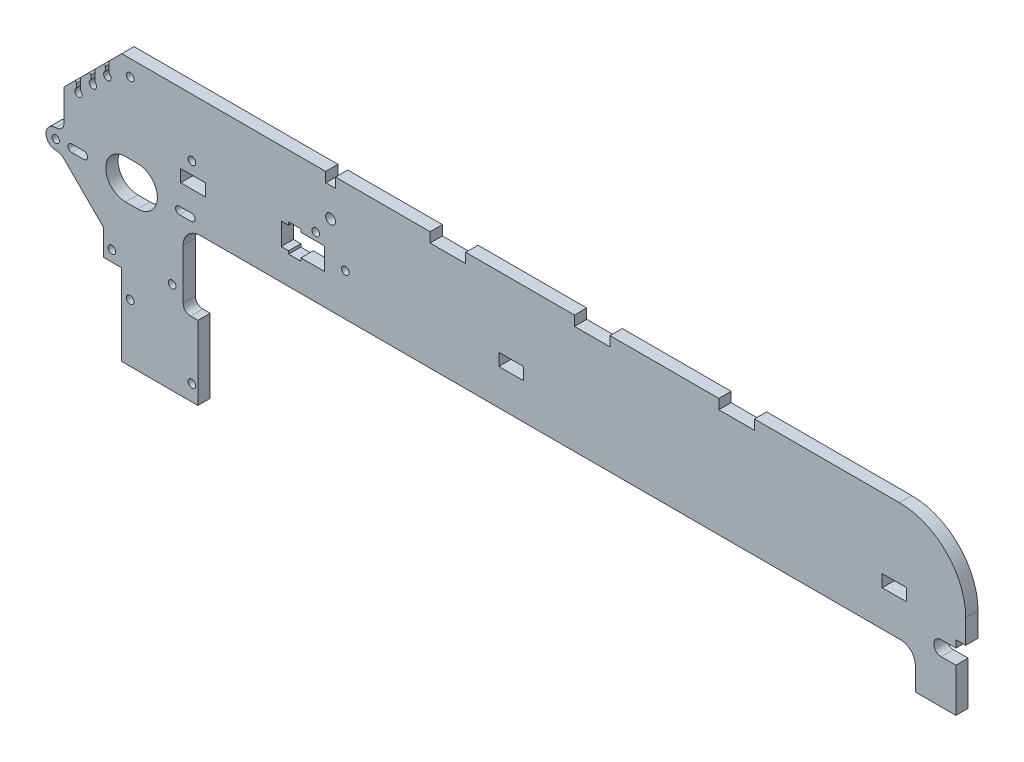
SolidWorks part; units mm, degrees
material "6061-T6 Black anodised"
ref_plane "Front Plane" through (0, 0, 0) normal (0, 0, 1) x (1, 0, 0)
ref_plane "Top Plane" through (0, 0, 0) normal (0, 1, 0) x (1, 0, 0)
ref_plane "Right Plane" through (0, 0, 0) normal (1, 0, 0) x (0, 0, -1)
sketch "Sketch1" plane through (0, 0, 0) normal (0, 0, 1) x (1, 0, 0)
  line L0 (-19.5, 0) -> (36.1968, 0) construction
  line L1 (-1.5, 32) -> (20.5, 32) construction
  line L2 (-21.9203, 0) -> (-30, 0) construction
  line L3 (-6.5, 43.5) -> (-6.5, 28.8553) construction
  line L4 (-1.5, 43.5) -> (20.5, 43.5) construction
  line L5 (310, 43.5) -> (251, 43.5)
  line L6 (21.9203, 0) -> (0, 21.9203) construction
  line L7 (0, 21.9203) -> (-21.9203, 0) construction
  line L8 (-21.9203, 0) -> (0, -21.9203) construction
  line L9 (0, -21.9203) -> (21.9203, 0) construction
  line L10 (316.5, -4.6) -> (316.5, -20)
  line L11 (-6.5, -65) -> (-6.5, -32)
  line L12 (-30, 5.3553) -> (-30, -5.3553) construction
  line L13 (327, 3.7) -> (333, 3.7)
  line L14 (316.5, -20) -> (333, -20)
  line L15 (18.5, -4.6) -> (316.5, -4.6)
  line L16 (34.5, -11.1) -> (59.432, -11.1) construction
  line L17 (333, 6.7) -> (333, 3.7)
  line L18 (9.5, 43.5) -> (9.5, -35.4767) construction
  line L19 (-1.5, 43.5) -> (20.5, 43.5) construction
  line L20 (-1.5, 43.5) -> (-1.5, 20.5) construction
  line L21 (-6.5, -65) -> (24.5, -65)
  line L22 (-1.5, 20.5) -> (20.5, 20.5) construction
  line L23 (327, -2.3) -> (333, -2.3)
  line L24 (333, -2.3) -> (333, -20)
  line L25 (333, 6.7) -> (337, 6.7)
  line L26 (337, 6.7) -> (337, 16.5)
  line L27 (18.5, -35) -> (18.5, -4.6)
  line L28 (20.5, 43.5) -> (20.5, 20.5) construction
  line L29 (17.5, 15) -> (17.5, 10)
  line L30 (17.5, 15) -> (27.5, 15)
  line L31 (27, 72.5933) -> (67, 72.5933) construction
  line L32 (147, 10) -> (157, 10)
  line L33 (147, 10) -> (147, 15)
  line L34 (17.5, 10) -> (27.5, 10)
  line L35 (27.5, 15) -> (27.5, 10)
  line L36 (147, 15) -> (157, 15)
  line L37 (157, 10) -> (157, 15)
  line L38 (303, 10) -> (313, 10)
  line L39 (303, 10) -> (303, 15)
  line L40 (303, 15) -> (313, 15)
  line L41 (313, 10) -> (313, 15)
  line L42 (27, 72.5933) -> (27, -81.6129) construction
  line L43 (27, -81.6129) -> (67, -81.6129) construction
  line L44 (67, 72.5933) -> (67, -81.6129) construction
  line L45 (-1.5, -52.5) -> (20.5, -52.5) construction
  line L46 (-1.5, -65) -> (20.5, -65) construction
  line L47 (-1.5, -65) -> (-1.5, -42) construction
  line L48 (-1.5, -42) -> (20.5, -42) construction
  line L49 (20.5, -65) -> (20.5, -42) construction
  line L50 (58.4277, 8) -> (61.4277, 8)
  line L51 (27.5, 12.5) -> (63.9277, 12.5) construction
  line L52 (61.4277, 6.8061) -> (66.4277, 6.8061)
  line L53 (61.4277, 6.8061) -> (61.4277, 8)
  line L54 (76, 8) -> (76, 17)
  line L55 (72.5, 20.1) -> (72.5, 7.1) construction
  line L56 (66.4277, 6.8061) -> (66.4277, 8)
  line L57 (66.4277, 8) -> (76, 8)
  line L58 (63.9277, 12.5) -> (76, 12.5) construction
  line L59 (66.4277, 18.1939) -> (61.4277, 18.1939)
  line L60 (66.4277, 6.8061) -> (61.4277, 18.1939) construction
  line L61 (61.4277, 6.8061) -> (66.4277, 18.1939) construction
  line L62 (18.5, -35) -> (24.5, -35)
  line L63 (66.4277, 17) -> (66.4277, 18.1939)
  line L64 (66.4277, 17) -> (76, 17)
  line L65 (61.4277, 17) -> (61.4277, 18.1939)
  line L66 (24.5, -35) -> (24.5, -65)
  line L67 (-14, -21.3553) -> (-30, -5.3553)
  line L68 (-14, -21.3553) -> (-14, -32)
  line L69 (-14, -32) -> (-6.5, -32)
  line L70 (119, 43.5) -> (119, 39.5)
  line L71 (119, 39.5) -> (133.5, 39.5)
  line L72 (177.75, 43.5) -> (177.75, 39.5)
  line L73 (119, 43.5) -> (80.5, 43.5)
  line L74 (-6.5, 28.8553) -> (-30, 5.3553) construction
  line L75 (177.75, 39.5) -> (192.25, 39.5)
  line L76 (159.788, -14) -> (-14, -14) construction
  line L77 (159.788, -14) -> (159.788, -26) construction
  line L78 (61.4277, 17) -> (58.4277, 17)
  line L79 (159.788, -26) -> (-14, -26) construction
  line L80 (-14, -14) -> (-14, -26) construction
  line L81 (58.4277, 17) -> (58.4277, 8)
  line L82 (159.788, -14) -> (-14, -26) construction
  line L83 (159.788, -26) -> (-14, -14) construction
  line L84 (192.25, 39.5) -> (192.25, 43.5)
  line L86 (236.5, 43.5) -> (236.5, 39.5)
  line L87 (236.5, 39.5) -> (251, 39.5)
  line L88 (251, 39.5) -> (251, 43.5)
  line L89 (177.75, 43.5) -> (133.5, 43.5)
  line L91 (-33.3631, 8.7185) -> (-33.3631, -8.7185) construction
  line L92 (76.5, 27.7514) -> (80.5, 27.7514) construction
  line L93 (133.5, 39.5) -> (133.5, 43.5)
  line L94 (76.5, 43.5) -> (76.5, 39.5)
  line L95 (76.5, 39.5) -> (80.5, 39.5)
  line L96 (80.5, 43.5) -> (80.5, 39.5)
  line L97 (76.5, 43.5) -> (-6.5, 43.5)
  line L98 (-30, 20) -> (-6.5, 43.5)
  line L99 (-30, 20) -> (-30, 7.3254)
  line L101 (119, 43.5) -> (177.75, 43.5) construction
  line L102 (192.25, 43.5) -> (236.5, 43.5)
  circle A0 centre (9.5, 34.5) radius 1.55 construction
  circle A1 centre (0, 0) radius 15.5 construction
  circle A2 centre (0, 21.9203) radius 1.5 construction
  circle A3 centre (21.9203, 0) radius 1.5
  circle A4 centre (0, -21.9203) radius 1.5 construction
  circle A5 centre (-21.9203, 0) radius 1.5
  circle A6 centre (0, 0) radius 5.5 construction
  arc A7 (337, 16.5) -> (310, 43.5) centre (310, 16.5) ccw
  circle A8 centre (0, 0) radius 8
  circle A9 centre (-3.05, 37) radius 1.55
  circle A10 centre (9.5, -57) radius 1.55 construction
  arc A11 (327, 3.7) -> (327, -2.3) centre (327, 0.7) ccw
  circle A12 centre (72, 0.4) radius 5 construction
  circle A13 centre (22, 38.5) radius 5 construction
  circle A14 centre (22, 38.5) radius 1.5 construction
  circle A15 centre (72, 0.4) radius 1.5 construction
  circle A16 centre (22.05, 20) radius 1.55
  circle A17 centre (-3.05, -41.5) radius 1.55
  circle A18 centre (22.05, -58.5) radius 1.55
  circle A19 centre (81.5, 20.1) radius 1.55 construction
  circle A20 centre (72.5, 20.1) radius 1.55
  circle A21 centre (84.5, 12.5) radius 1.55
  circle A22 centre (-10.5, -27.55) radius 1.55
  arc A23 (-33.3631, 3.9623) -> (-33.3631, -3.9623) centre (-33.3631, 0) ccw
  circle A24 centre (14, -27.55) radius 1.55
  circle A25 centre (-33.3631, 0) radius 1.5
  arc A26 (-33.3631, 3.9623) -> (-30, 7.3254) centre (-33.3631, 7.3254) ccw
  arc A27 (-33.3631, -3.9623) -> (-30, -5.3553) centre (-33.3631, -8.7185) cw
  circle A28 centre (78.5, 27.7514) radius 2
  point P18 (26.8692, -2.8293)
  point P19 (26.8692, 2.8293)
  point P108 (58.4277, 12.5)
  point P115 (72.894, -20)
  dimension "D2" = 31
  dimension "D3" = 3
  dimension "D4" = 11
  dimension "D12" = 16
  dimension "D20" = 3.1
  dimension "D22" = 8
  dimension "D25" = 3
  dimension "D28" = 6
  dimension "D32" = 10
  dimension "D38" = 3
  dimension "D14" = 31
  dimension "D41" = 3.1
  dimension "D44" = 9
  dimension "D45" = 3.1
  dimension "D53" = 6
  dimension "D18" = 7.5
  dimension "D57" = 3.1
  dimension "D69" = 4
  dimension "D7" = 9
  dimension "D11" = 16.5
  dimension "D17" = 15
  dimension "D8" = 65
  dimension "D9" = 43.5
  dimension "D5" = 9.5
  dimension "D6" = 4.6
  dimension "D10" = 6.5
  dimension "D13" = 337
  dimension "D15" = 23
  dimension "D16" = 25
  dimension "D19" = 30
  dimension "D21" = 9
  dimension "D23" = 21.1
  dimension "D24" = 15.4
  dimension "D26" = 6
  dimension "D27" = 4
  dimension "D29" = 67
  dimension "D30" = 17.5
  dimension "D31" = 40
  dimension "D33" = 5
  dimension "D34" = 10
  dimension "D35" = 24
  dimension "D36" = 180
  dimension "D37" = 22
  dimension "D39" = 5
  dimension "D40" = 12
  dimension "D42" = 11
  dimension "D43" = 6
  dimension "D46" = 3.1
  dimension "D47" = 9
  dimension "D48" = 15
  dimension "D49" = 0.7
  dimension "D50" = 5
  dimension "D51" = 12
  dimension "D52" = 3.5
  dimension "D54" = 4
  dimension "D55" = 12
  dimension "D56" = 20
  dimension "D58" = 4.5
  dimension "D59" = 3
  dimension "D60" = 9
  dimension "D61" = 30
  dimension "D62" = 12.5
  dimension "D63" = 52
  dimension "D64" = 14.5
  dimension "D68" = 4
  dimension "D70" = 6
  dimension "D72" = 58.75
  dimension "D67" = 3
extrude "Boss-Extrude1" add sketch "Sketch1" along normal blind 5
fillet "Fillet1" [suppressed] radius 8
fillet "Fillet2" radius 7 1 edges at (18.5, -4.6, 2.5)
fillet "Fillet3" radius 3 1 edges at (18.5, -35, 2.5)
sketch "Sketch2" plane through (0, 0, 5) normal (0, 0, 1) x (1, 0, 0)
  line L0 (21.9203, 0) -> (16.9203, 0) construction
  line L1 (21.9203, -1.5) -> (16.9203, -1.5)
  line L2 (21.9203, 1.5) -> (16.9203, 1.5)
  line L3 (0, 0) -> (-5, 0) construction
  line L4 (0, -8) -> (-5, -8)
  line L5 (0, 8) -> (-5, 8)
  line L6 (-21.9203, 0) -> (-26.9203, 0) construction
  line L7 (-21.9203, -1.5) -> (-26.9203, -1.5)
  line L8 (-21.9203, 1.5) -> (-26.9203, 1.5)
  arc A0 (21.9203, -1.5) -> (21.9203, 1.5) centre (21.9203, 0) ccw
  arc A1 (16.9203, 1.5) -> (16.9203, -1.5) centre (16.9203, 0) ccw
  arc A2 (0, -8) -> (0, 8) centre (0, 0) ccw
  arc A3 (-5, 8) -> (-5, -8) centre (-5, 0) ccw
  arc A4 (-21.9203, -1.5) -> (-21.9203, 1.5) centre (-21.9203, 0) ccw
  arc A5 (-26.9203, 1.5) -> (-26.9203, -1.5) centre (-26.9203, 0) ccw
  circle A6 centre (21.9203, 0) radius 1.5 construction
  circle A7 centre (0, 0) radius 8 construction
  point P4 (19.4203, 0)
  point P9 (-2.5, 0)
  point P16 (-24.4203, 0)
  dimension "D1" = 5
extrude "Cut-Extrude1" cut sketch "Sketch2" against normal through all
fillet "Fillet4" radius 6 1 edges at (316.5, -4.6, 2.5)
sketch "Sketch3" plane through (0, 0, 5) normal (0, 0, 1) x (1, 0, 0)
  line L0 (-12.375, 32.625) -> (-12.375, 37.625) construction
  line L1 (-13.125, 42.8359) -> (-11.625, 42.8359)
  line L2 (-13.125, 42.8359) -> (-13.125, 33.924)
  line L3 (-6.5, 43.5) -> (-30, 20) construction
  line L4 (-11.625, 42.8359) -> (-11.625, 33.924)
  line L5 (-13.125, 42.8359) -> (-11.625, 33.924) construction
  line L6 (-13.125, 33.924) -> (-11.625, 42.8359) construction
  line L7 (-6.5, 43.5) -> (-12.375, 37.625) construction
  line L8 (-12.375, 37.625) -> (-18.25, 31.75) construction
  line L9 (-18.25, 31.75) -> (-24.125, 25.875) construction
  line L10 (-24.125, 25.875) -> (-30, 20) construction
  line L11 (-17.4, 36.9218) -> (-17.4, 27.9859)
  line L12 (-18.25, 26.75) -> (-18.25, 31.75) construction
  line L13 (-19.1, 36.9218) -> (-17.4, 27.9859) construction
  line L14 (-19.1, 27.9859) -> (-17.4, 36.9218) construction
  line L15 (-19.1, 36.9218) -> (-19.1, 27.9859)
  line L16 (-19.1, 36.9218) -> (-17.4, 36.9218)
  line L17 (-23.275, 31.0468) -> (-23.275, 22.1109)
  line L18 (-24.975, 31.0468) -> (-23.275, 22.1109) construction
  line L19 (-24.975, 22.1109) -> (-23.275, 31.0468) construction
  line L20 (-24.975, 31.0468) -> (-23.275, 31.0468)
  line L21 (-24.125, 20.875) -> (-24.125, 25.875) construction
  line L22 (-24.975, 31.0468) -> (-24.975, 22.1109)
  arc A0 (-13.125, 33.924) -> (-11.625, 33.924) centre (-12.375, 32.625) ccw
  arc A1 (-19.1, 27.9859) -> (-17.4, 27.9859) centre (-18.25, 26.75) ccw
  arc A2 (-24.975, 22.1109) -> (-23.275, 22.1109) centre (-24.125, 20.875) ccw
  point P0 (-12.375, 38.3799)
  point P15 (-18.25, 32.4539)
  point P22 (-24.125, 26.5789)
  dimension "D1" = 1.5
  dimension "D2" = 1.5
  dimension "D3" = 5
extrude "Cut-Extrude2" cut sketch "Sketch3" against normal through all
fillet "Fillet5" radius 0.5 3 edges at (-24.975, 25.025, 2.5) (-19.1, 30.9, 2.5) (-13.125, 36.875, 2.5)
equation "\"y-plate-thickness\"=5"
equation "\"bed-plate-thickness\"=3"
equation "\"x-plate-thickness\"=5"
equation "\"D1@Boss-Extrude1\"=\"x-plate-thickness\""
equation "\"D33@Sketch1\"=\"x-plate-thickness\""
